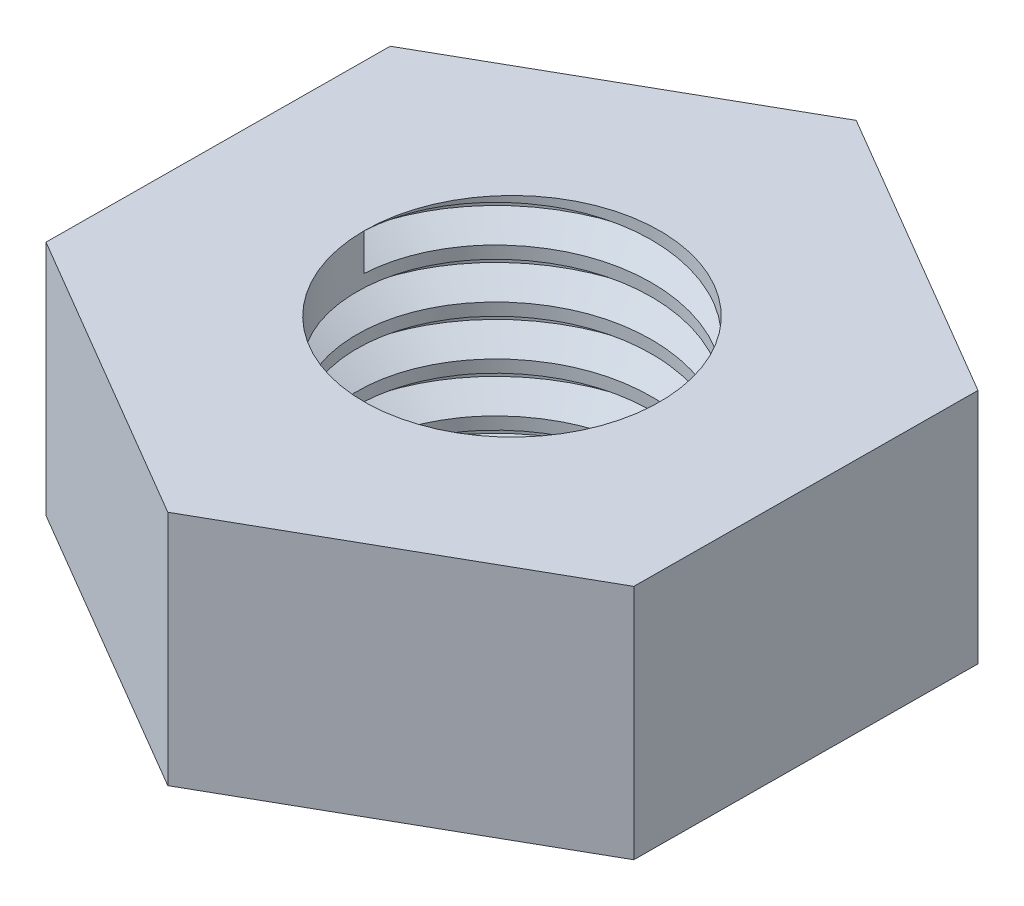
SolidWorks part; units mm, degrees
material "AISI Type A2 Tool Steel"
ref_plane "Front Plane" through (0, 0, 0) normal (0, 0, 1) x (1, 0, 0)
ref_plane "Top Plane" through (0, 0, 0) normal (0, 1, 0) x (1, 0, 0)
ref_plane "Right Plane" through (0, 0, 0) normal (1, 0, 0) x (0, 0, -1)
sketch "Sketch1" plane through (0, 0, 0) normal (0, 1, 0) x (1, 0, 0)
  line L1 (3.0122, 1.7108) -> (0.0245, 3.464)
  line L2 (0.0245, 3.464) -> (-2.9877, 1.7532)
  line L3 (-2.9877, 1.7532) -> (-3.0122, -1.7108)
  line L4 (-3.0122, -1.7108) -> (-0.0245, -3.464)
  line L5 (-0.0245, -3.464) -> (2.9877, -1.7532)
  line L6 (2.9877, -1.7532) -> (3.0122, 1.7108)
  circle A0 centre (0, 0) radius 3 construction
  dimension "D1" = 6
extrude "Boss-Extrude1" add sketch "Sketch1" along normal blind 2.4
sketch "Sketch2" plane through (0, 2.4, 0) normal (0, 1, 0) x (1, 0, 0)
  circle A0 centre (0, 0) radius 1.5
  dimension "D1" = 3
extrude "Cut-Extrude1" cut sketch "Sketch2" against normal blind 2.4
thread "Thread2" pitch 0.5 method cut profile "Thread Profile2" start angle 0, offset 0, length 0, pitch 0.5, diameter 3
ref_plane "Plane2" through (-1.5, 2.4, 0) normal (0, 0, 1) x (-1, 0, 0)
sketch "Thread Profile2" plane through (-1.5, 2.4, 0) normal (0, 0, 1) x (-1, 0, 0)
  line L0 (0, 0) -> (0, 0.5) construction
  line L1 (0, 0) -> (0.2706, 0.1562)
  line L2 (0.2706, 0.1562) -> (0.2706, 0.2187)
  line L3 (0.2706, 0.2187) -> (0, 0.375)
  line L4 (0.2706, 0.1875) -> (0, 0.1875) construction
  line L11 (0, 0) -> (0, 0.375)
  point P2 (0, 0)
  dimension "Pitch" = 0.5
  dimension "Profile_Angle" = 60
  dimension "Profile_Land" = 0.0625
  dimension "Profile_Height" = 0.2706
